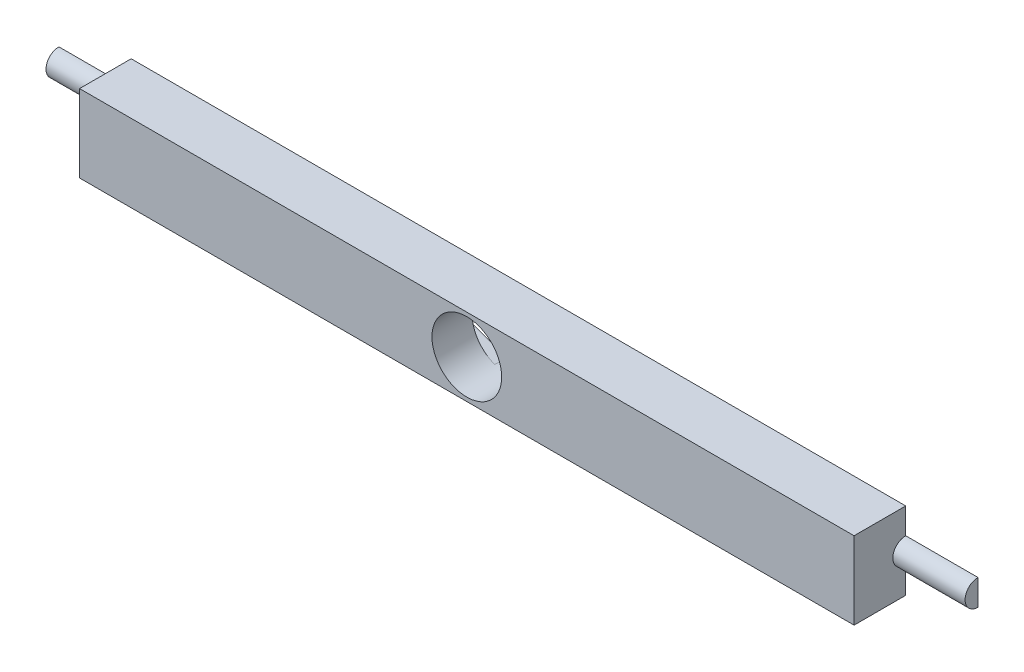
SolidWorks part; units mm, degrees
ref_plane "前视基准面" through (0, 0, 0) normal (0, 0, 1) x (1, 0, 0)
ref_plane "上视基准面" through (0, 0, 0) normal (0, 1, 0) x (1, 0, 0)
ref_plane "右视基准面" through (0, 0, 0) normal (1, 0, 0) x (0, 0, -1)
other "Configuration Table"
sketch "草图1" plane through (0, 0, 0) normal (0, 0, 1) x (1, 0, 0)
  line L0 (0, 0) -> (79.8665, 0) construction
  line L1 (0, 0) -> (0, 25.0088) construction
  line L2 (-150, 0) -> (-150, 30)
  line L3 (-150, 30) -> (150, 30)
  line L4 (150, 30) -> (150, 0)
  line L5 (150, 0) -> (-150, 0)
  point P7 (0, 30)
  dimension "D1" = 300
  dimension "D2" = 30
extrude "凸台-拉伸1" add sketch "草图1" along normal blind 20 contours L2 L3 L4 L5
sketch "草图2" plane through (-150, 0, 0) normal (-1, 0, 0) x (0, 0, 1)
  line L0 (0, 0) -> (0, 30) construction
  line L3 (0, 15) -> (20, 15) construction
  line L6 (0, 20) -> (0, 10)
  line L8 (0, 0) -> (0, 30) construction
  arc A0 (0, 10) -> (0, 20) centre (0, 15) ccw
  dimension "D1" = 5
extrude "凸台-拉伸2" add sketch "草图2" along normal blind 28 and the other way blind 328 contours L6 A0
sketch "草图3" plane through (0, 0, 0) normal (0, 0, -1) x (-1, 0, 0)
  line L0 (0, 0) -> (0, 154.9902) construction
  line L1 (-178, 15) -> (178, 15) construction
  line L3 (4.6895, 27.6593) -> (25.5737, 19.9231)
  line L4 (4.6895, 2.3407) -> (25.5737, 10.0769)
  line L5 (-4.6895, 2.3407) -> (-25.5737, 10.0769)
  line L6 (-4.6895, 27.6593) -> (-25.5737, 19.9231)
  circle A0 centre (0, 15) radius 13.5
  arc A1 (25.5737, 10.0769) -> (25.5737, 19.9231) centre (23.75, 15) ccw
  circle A2 centre (0, 15) radius 4
  circle A3 centre (0, 15) radius 6
  arc A4 (-25.5737, 10.0769) -> (-25.5737, 19.9231) centre (-23.75, 15) cw
  circle A5 centre (-23.75, 15) radius 2.4
  circle A6 centre (23.75, 15) radius 2.4
  dimension "D1" = 27
  dimension "D2" = 8
  dimension "D3" = 12
  dimension "D5" = 10.5
  dimension "D6" = 4.8
  dimension "D4" = 23.75
extrude "切除-拉伸2" cut sketch "草图3" against normal through all contours A3 A2 | A2 | A0 A3 region at (-10.7672, 22.4936, 0) region at (0, 15, 0) region at (5.8303, 15, 0)
extrude "切除-拉伸3" cut sketch "草图3<4>" against normal blind 4.5 contours L4 A1 L3 A0 | A4 L5 A0 L6 region at (-18.3267, 15, 0) region at (18.3267, 15, 0)
sketch "草图3<4>" plane through (0, 0, 0) normal (0, 0, -1) x (-1, 0, 0) same geometry as "草图3"
extrude "切除-拉伸4" cut sketch "草图3<5>" against normal blind 5 contours A5 | A6 region at (23.75, 15, 0) region at (-23.75, 15, 0)
sketch "草图3<5>" plane through (0, 0, 0) normal (0, 0, -1) x (-1, 0, 0) same geometry as "草图3"
